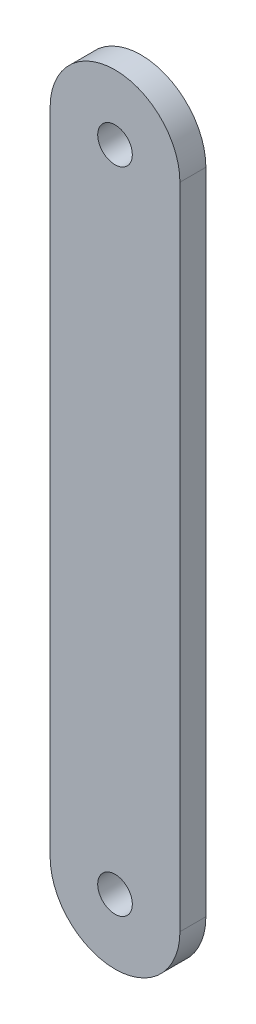
SolidWorks part; units mm, degrees
ref_plane "Front Plane" through (0, 0, 0) normal (0, 0, 1) x (1, 0, 0)
ref_plane "Top Plane" through (0, 0, 0) normal (0, 1, 0) x (1, 0, 0)
ref_plane "Right Plane" through (0, 0, 0) normal (1, 0, 0) x (0, 0, -1)
sketch "Sketch1" plane through (0, 0, 0) normal (0, 0, 1) x (1, 0, 0)
  line L2 (185.8254, 60.5329) -> (185.8254, 135.5329)
  line L4 (200.8254, 60.5329) -> (200.8254, 135.5329)
  arc A0 (185.8254, 60.5329) -> (200.8254, 60.5329) centre (193.3254, 60.5329) ccw
  arc A1 (200.8254, 135.5329) -> (185.8254, 135.5329) centre (193.3254, 135.5329) ccw
  circle A2 centre (193.3254, 60.5329) radius 2
  circle A3 centre (193.3254, 135.5329) radius 2
  dimension "D3" = 4
  dimension "D4" = 4
  dimension "D1" = 15
  dimension "D2" = 75
extrude "Boss-Extrude1" add sketch "Sketch1" along normal blind 3
